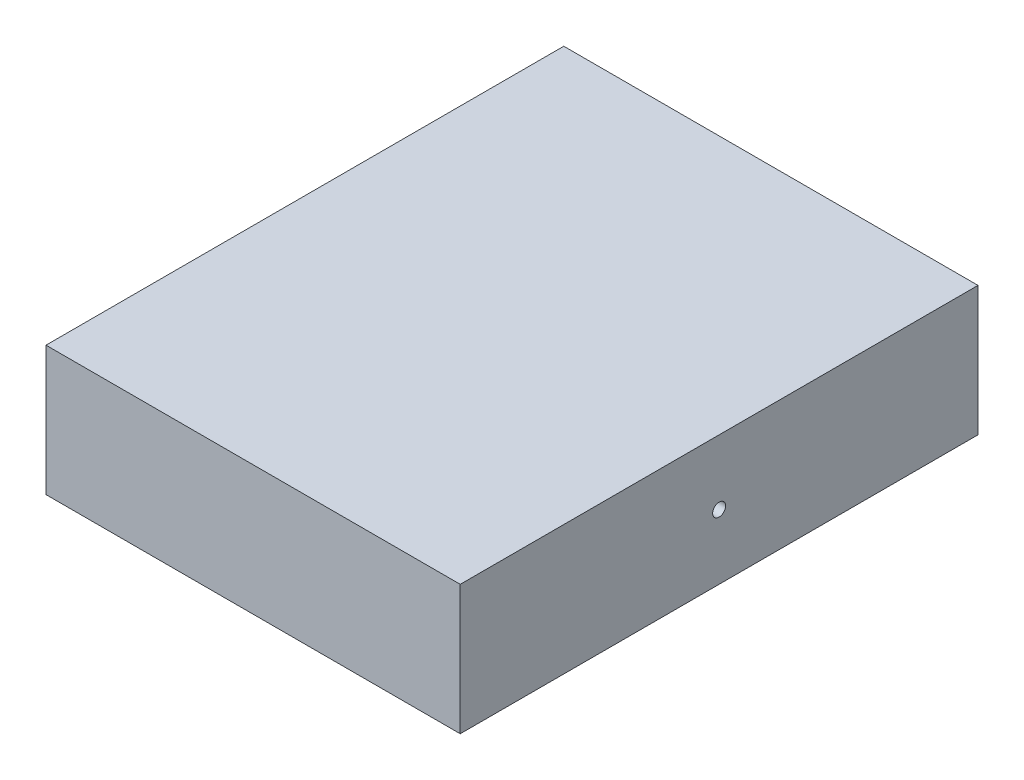
SolidWorks part; units mm, degrees
ref_plane "Front Plane" through (0, 0, 0) normal (0, 0, 1) x (1, 0, 0)
ref_plane "Top Plane" through (0, 0, 0) normal (0, 1, 0) x (1, 0, 0)
ref_plane "Right Plane" through (0, 0, 0) normal (1, 0, 0) x (0, 0, -1)
sketch "Sketch1" plane through (0, 0, 0) normal (0, 0, 1) x (1, 0, 0)
  line L1 (0, 0) -> (406.4, 0)
  line L2 (0, 0) -> (0, 127)
  line L3 (0, 127) -> (406.4, 127)
  line L4 (406.4, 0) -> (406.4, 127)
  dimension "D1" = 406.4
  dimension "D2" = 127
extrude "Boss-Extrude1" add sketch "Sketch1" along normal blind 508
sketch "Sketch2" plane through (406.4, 0, 0) normal (1, 0, 0) x (0, 0, -1)
  line L0 (-508, 0) -> (0, 127) construction
  line L1 (0, 127) -> (0, 0) construction
  line L2 (0, 0) -> (-508, 127) construction
  circle A0 centre (-254, 63.5) radius 6.35
  dimension "D1" = 12.7
extrude "Cut-Extrude1" cut sketch "Sketch2" against normal through all
